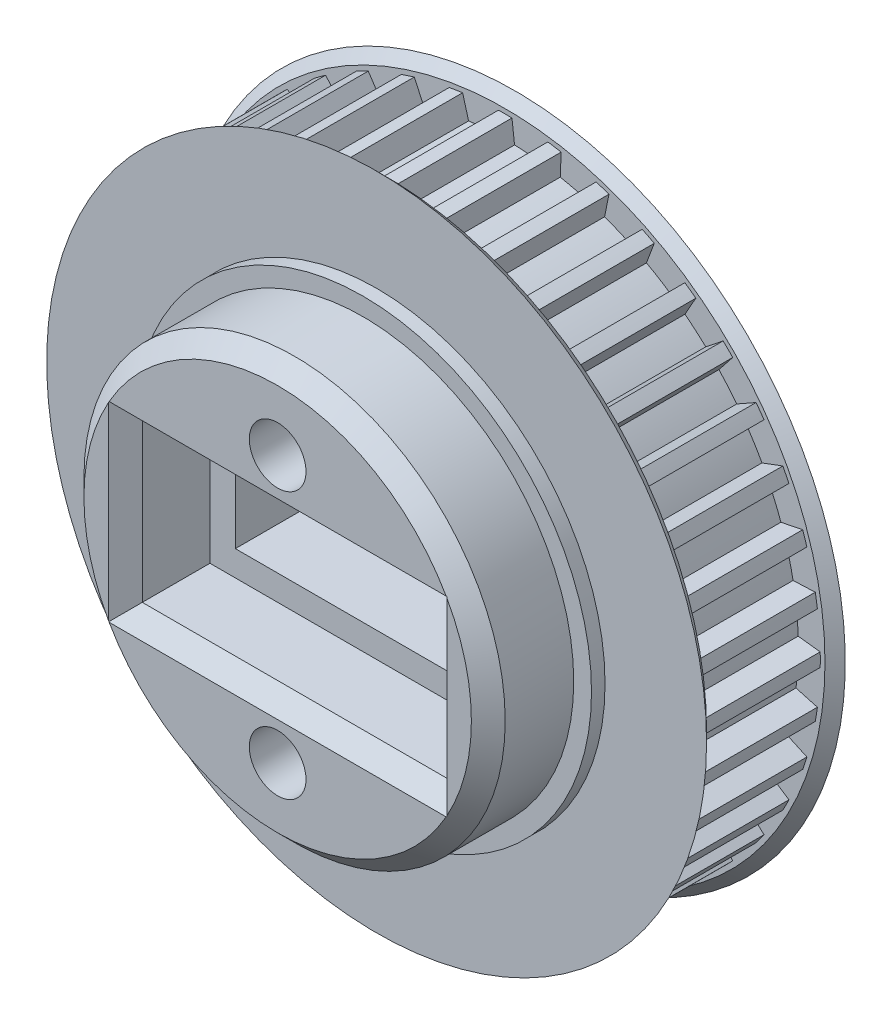
SolidWorks part; units mm, degrees
material "ABS"
ref_plane "Alzado" through (0, 0, 0) normal (0, 0, 1) x (1, 0, 0)
ref_plane "Planta" through (0, 0, 0) normal (0, 1, 0) x (1, 0, 0)
ref_plane "Vista lateral" through (0, 0, 0) normal (1, 0, 0) x (0, 0, -1)
sketch "Croquis1" plane through (0, 0, 0) normal (0, 0, 1) x (1, 0, 0)
  line L0 (0, 0) -> (0, 14.5885) construction
  line L1 (-0.4, 18.6167) -> (-0.55, 17.3123)
  line L2 (0.4, 18.6167) -> (0.55, 17.3123)
  line L3 (3.3074, 18.3249) -> (3.2515, 17.0131)
  line L4 (2.5172, 18.4501) -> (2.165, 17.1852)
  line L5 (6.1333, 17.5819) -> (5.8729, 16.295)
  line L6 (5.3725, 17.8291) -> (4.8267, 16.6349)
  line L7 (8.8082, 16.406) -> (8.3497, 15.1756)
  line L8 (8.0954, 16.7692) -> (7.3695, 15.675)
  line L9 (11.2662, 14.8261) -> (10.6209, 13.6826)
  line L10 (10.619, 15.2963) -> (9.7309, 14.3292)
  line L11 (13.4468, 12.8812) -> (12.6305, 11.8527)
  line L12 (12.8812, 13.4468) -> (11.8527, 12.6305)
  line L13 (15.2963, 10.619) -> (14.3292, 9.7309)
  line L14 (14.8261, 11.2662) -> (13.6826, 10.6209)
  line L15 (16.7692, 8.0954) -> (15.675, 7.3695)
  line L16 (16.406, 8.8082) -> (15.1756, 8.3497)
  line L17 (17.8291, 5.3725) -> (16.6349, 4.8267)
  line L18 (17.5819, 6.1333) -> (16.295, 5.8729)
  line L19 (18.4501, 2.5172) -> (17.1852, 2.165)
  line L20 (18.3249, 3.3074) -> (17.0131, 3.2515)
  line L21 (18.6167, -0.4) -> (17.3123, -0.55)
  line L22 (18.6167, 0.4) -> (17.3123, 0.55)
  line L23 (18.3249, -3.3074) -> (17.0131, -3.2515)
  line L24 (18.4501, -2.5172) -> (17.1852, -2.165)
  line L25 (17.5819, -6.1333) -> (16.295, -5.8729)
  line L26 (17.8291, -5.3725) -> (16.6349, -4.8267)
  line L27 (16.406, -8.8082) -> (15.1756, -8.3497)
  line L28 (16.7692, -8.0954) -> (15.675, -7.3695)
  line L29 (14.8261, -11.2662) -> (13.6826, -10.6209)
  line L30 (15.2963, -10.619) -> (14.3292, -9.7309)
  line L31 (12.8812, -13.4468) -> (11.8527, -12.6305)
  line L32 (13.4468, -12.8812) -> (12.6305, -11.8527)
  line L33 (10.619, -15.2963) -> (9.7309, -14.3292)
  line L34 (11.2662, -14.8261) -> (10.6209, -13.6826)
  line L35 (8.0954, -16.7692) -> (7.3695, -15.675)
  line L36 (8.8082, -16.406) -> (8.3497, -15.1756)
  line L37 (5.3725, -17.8291) -> (4.8267, -16.6349)
  line L38 (6.1333, -17.5819) -> (5.8729, -16.295)
  line L39 (2.5172, -18.4501) -> (2.165, -17.1852)
  line L40 (3.3074, -18.3249) -> (3.2515, -17.0131)
  line L41 (-0.4, -18.6167) -> (-0.55, -17.3123)
  line L42 (0.4, -18.6167) -> (0.55, -17.3123)
  line L43 (-3.3074, -18.3249) -> (-3.2515, -17.0131)
  line L44 (-2.5172, -18.4501) -> (-2.165, -17.1852)
  line L45 (-6.1333, -17.5819) -> (-5.8729, -16.295)
  line L46 (-5.3725, -17.8291) -> (-4.8267, -16.6349)
  line L47 (-8.8082, -16.406) -> (-8.3497, -15.1756)
  line L48 (-8.0954, -16.7692) -> (-7.3695, -15.675)
  line L49 (-11.2662, -14.8261) -> (-10.6209, -13.6826)
  line L50 (-10.619, -15.2963) -> (-9.7309, -14.3292)
  line L51 (-13.4468, -12.8812) -> (-12.6305, -11.8527)
  line L52 (-12.8812, -13.4468) -> (-11.8527, -12.6305)
  line L53 (-15.2963, -10.619) -> (-14.3292, -9.7309)
  line L54 (-14.8261, -11.2662) -> (-13.6826, -10.6209)
  line L55 (-16.7692, -8.0954) -> (-15.675, -7.3695)
  line L56 (-16.406, -8.8082) -> (-15.1756, -8.3497)
  line L57 (-17.8291, -5.3725) -> (-16.6349, -4.8267)
  line L58 (-17.5819, -6.1333) -> (-16.295, -5.8729)
  line L59 (-18.4501, -2.5172) -> (-17.1852, -2.165)
  line L60 (-18.3249, -3.3074) -> (-17.0131, -3.2515)
  line L61 (-18.6167, 0.4) -> (-17.3123, 0.55)
  line L62 (-18.6167, -0.4) -> (-17.3123, -0.55)
  line L63 (-18.3249, 3.3074) -> (-17.0131, 3.2515)
  line L64 (-18.4501, 2.5172) -> (-17.1852, 2.165)
  line L65 (-17.5819, 6.1333) -> (-16.295, 5.8729)
  line L66 (-17.8291, 5.3725) -> (-16.6349, 4.8267)
  line L67 (-16.406, 8.8082) -> (-15.1756, 8.3497)
  line L68 (-16.7692, 8.0954) -> (-15.675, 7.3695)
  line L69 (-14.8261, 11.2662) -> (-13.6826, 10.6209)
  line L70 (-15.2963, 10.619) -> (-14.3292, 9.7309)
  line L71 (-12.8812, 13.4468) -> (-11.8527, 12.6305)
  line L72 (-13.4468, 12.8812) -> (-12.6305, 11.8527)
  line L73 (-10.619, 15.2963) -> (-9.7309, 14.3292)
  line L74 (-11.2662, 14.8261) -> (-10.6209, 13.6826)
  line L75 (-8.0954, 16.7692) -> (-7.3695, 15.675)
  line L76 (-8.8082, 16.406) -> (-8.3497, 15.1756)
  line L77 (-5.3725, 17.8291) -> (-4.8267, 16.6349)
  line L78 (-6.1333, 17.5819) -> (-5.8729, 16.295)
  line L79 (-11.2662, 14.8261) -> (-10.619, 15.2963)
  line L80 (-8.8082, 16.406) -> (-8.0954, 16.7692)
  line L81 (-6.1333, 17.5819) -> (-5.3725, 17.8291)
  line L82 (-2.5172, 18.4501) -> (-2.165, 17.1852)
  line L83 (-3.3074, 18.3249) -> (-3.2515, 17.0131)
  line L84 (-3.3074, 18.3249) -> (-2.5172, 18.4501)
  arc A0 (-17.5819, 6.1333) -> (-17.8291, 5.3725) centre (0, 0) ccw
  arc A1 (2.165, 17.1852) -> (0.55, 17.3123) centre (0, 0) ccw
  arc A2 (-18.3249, 3.3074) -> (-18.4501, 2.5172) centre (0, 0) ccw
  arc A3 (-18.6167, 0.4) -> (-18.6167, -0.4) centre (0, 0) ccw
  arc A4 (-18.4501, -2.5172) -> (-18.3249, -3.3074) centre (0, 0) ccw
  arc A5 (-17.8291, -5.3725) -> (-17.5819, -6.1333) centre (0, 0) ccw
  arc A6 (-16.7692, -8.0954) -> (-16.406, -8.8082) centre (0, 0) ccw
  arc A7 (-15.2963, -10.619) -> (-14.8261, -11.2662) centre (0, 0) ccw
  arc A8 (-13.4468, -12.8812) -> (-12.8812, -13.4468) centre (0, 0) ccw
  arc A9 (-11.2662, -14.8261) -> (-10.619, -15.2963) centre (0, 0) ccw
  arc A10 (-8.8082, -16.406) -> (-8.0954, -16.7692) centre (0, 0) ccw
  arc A11 (3.3074, 18.3249) -> (2.5172, 18.4501) centre (0, 0) ccw
  arc A12 (0.4, 18.6167) -> (-0.4, 18.6167) centre (0, 0) ccw
  arc A13 (-14.8261, 11.2662) -> (-15.2963, 10.619) centre (0, 0) ccw
  arc A14 (-16.406, 8.8082) -> (-16.7692, 8.0954) centre (0, 0) ccw
  arc A15 (-12.8812, 13.4468) -> (-13.4468, 12.8812) centre (0, 0) ccw
  arc A16 (6.1333, 17.5819) -> (5.3725, 17.8291) centre (0, 0) ccw
  arc A17 (8.8082, 16.406) -> (8.0954, 16.7692) centre (0, 0) ccw
  arc A18 (11.2662, 14.8261) -> (10.619, 15.2963) centre (0, 0) ccw
  arc A19 (13.4468, 12.8812) -> (12.8812, 13.4468) centre (0, 0) ccw
  arc A20 (15.2963, 10.619) -> (14.8261, 11.2662) centre (0, 0) ccw
  arc A21 (16.7692, 8.0954) -> (16.406, 8.8082) centre (0, 0) ccw
  arc A22 (17.8291, 5.3725) -> (17.5819, 6.1333) centre (0, 0) ccw
  arc A23 (18.4501, 2.5172) -> (18.3249, 3.3074) centre (0, 0) ccw
  arc A24 (18.6167, -0.4) -> (18.6167, 0.4) centre (0, 0) ccw
  arc A25 (18.3249, -3.3074) -> (18.4501, -2.5172) centre (0, 0) ccw
  arc A26 (12.8812, -13.4468) -> (13.4468, -12.8812) centre (0, 0) ccw
  arc A27 (10.619, -15.2963) -> (11.2662, -14.8261) centre (0, 0) ccw
  arc A28 (8.0954, -16.7692) -> (8.8082, -16.406) centre (0, 0) ccw
  arc A29 (2.5172, -18.4501) -> (3.3074, -18.3249) centre (0, 0) ccw
  arc A30 (-0.4, -18.6167) -> (0.4, -18.6167) centre (0, 0) ccw
  arc A31 (-3.3074, -18.3249) -> (-2.5172, -18.4501) centre (0, 0) ccw
  arc A32 (-6.1333, -17.5819) -> (-5.3725, -17.8291) centre (0, 0) ccw
  arc A33 (14.8261, -11.2662) -> (15.2963, -10.619) centre (0, 0) ccw
  arc A34 (16.406, -8.8082) -> (16.7692, -8.0954) centre (0, 0) ccw
  arc A35 (17.5819, -6.1333) -> (17.8291, -5.3725) centre (0, 0) ccw
  arc A36 (4.8267, 16.6349) -> (3.2515, 17.0131) centre (0, 0) ccw
  arc A37 (7.3695, 15.675) -> (5.8729, 16.295) centre (0, 0) ccw
  arc A38 (-12.6305, 11.8527) -> (-13.6826, 10.6209) centre (0, 0) ccw
  arc A39 (-0.55, 17.3123) -> (-2.165, 17.1852) centre (0, 0) ccw
  arc A40 (-14.3292, 9.7309) -> (-15.1756, 8.3497) centre (0, 0) ccw
  arc A41 (-15.675, 7.3695) -> (-16.295, 5.8729) centre (0, 0) ccw
  arc A42 (-16.6349, 4.8267) -> (-17.0131, 3.2515) centre (0, 0) ccw
  arc A43 (9.7309, 14.3292) -> (8.3497, 15.1756) centre (0, 0) ccw
  arc A44 (11.8527, 12.6305) -> (10.6209, 13.6826) centre (0, 0) ccw
  arc A45 (13.6826, 10.6209) -> (12.6305, 11.8527) centre (0, 0) ccw
  arc A46 (15.1756, 8.3497) -> (14.3292, 9.7309) centre (0, 0) ccw
  arc A47 (16.295, 5.8729) -> (15.675, 7.3695) centre (0, 0) ccw
  arc A48 (17.0131, 3.2515) -> (16.6349, 4.8267) centre (0, 0) ccw
  arc A49 (17.3123, 0.55) -> (17.1852, 2.165) centre (0, 0) ccw
  arc A50 (17.1852, -2.165) -> (17.3123, -0.55) centre (0, 0) ccw
  arc A51 (16.6349, -4.8267) -> (17.0131, -3.2515) centre (0, 0) ccw
  arc A52 (15.675, -7.3695) -> (16.295, -5.8729) centre (0, 0) ccw
  arc A53 (14.3292, -9.7309) -> (15.1756, -8.3497) centre (0, 0) ccw
  arc A54 (12.6305, -11.8527) -> (13.6826, -10.6209) centre (0, 0) ccw
  arc A55 (10.6209, -13.6826) -> (11.8527, -12.6305) centre (0, 0) ccw
  arc A56 (8.3497, -15.1756) -> (9.7309, -14.3292) centre (0, 0) ccw
  arc A57 (5.8729, -16.295) -> (7.3695, -15.675) centre (0, 0) ccw
  arc A58 (3.2515, -17.0131) -> (4.8267, -16.6349) centre (0, 0) ccw
  arc A59 (0.55, -17.3123) -> (2.165, -17.1852) centre (0, 0) ccw
  arc A60 (-2.165, -17.1852) -> (-0.55, -17.3123) centre (0, 0) ccw
  arc A61 (-4.8267, -16.6349) -> (-3.2515, -17.0131) centre (0, 0) ccw
  arc A62 (-7.3695, -15.675) -> (-5.8729, -16.295) centre (0, 0) ccw
  arc A63 (-9.7309, -14.3292) -> (-8.3497, -15.1756) centre (0, 0) ccw
  arc A64 (-11.8527, -12.6305) -> (-10.6209, -13.6826) centre (0, 0) ccw
  arc A65 (-13.6826, -10.6209) -> (-12.6305, -11.8527) centre (0, 0) ccw
  arc A66 (-15.1756, -8.3497) -> (-14.3292, -9.7309) centre (0, 0) ccw
  arc A67 (-16.295, -5.8729) -> (-15.675, -7.3695) centre (0, 0) ccw
  arc A68 (-17.0131, -3.2515) -> (-16.6349, -4.8267) centre (0, 0) ccw
  arc A69 (-17.3123, -0.55) -> (-17.1852, -2.165) centre (0, 0) ccw
  arc A70 (-17.1852, 2.165) -> (-17.3123, 0.55) centre (0, 0) ccw
  arc A71 (5.3725, -17.8291) -> (6.1333, -17.5819) centre (0, 0) ccw
  circle A72 centre (0, 0) radius 2
  arc A73 (-5.8729, 16.295) -> (-7.3695, 15.675) centre (0, 0) ccw
  arc A74 (-8.3497, 15.1756) -> (-9.7309, 14.3292) centre (0, 0) ccw
  arc A75 (-10.6209, 13.6826) -> (-11.8527, 12.6305) centre (0, 0) ccw
  arc A76 (-3.2515, 17.0131) -> (-4.8267, 16.6349) centre (0, 0) ccw
  point P151 (0, 0)
  dimension "D1" = 1.3
  dimension "D6" = 4
  dimension "D2" = 1.1
  dimension "D3" = 0.8
  dimension "D5" = 1.62
  dimension "D4" = 40
extrude "Saliente-Extruir1" add sketch "Croquis1" along normal blind 7
sketch "Croquis2" plane through (0, 0, 7) normal (0, 0, 1) x (1, 0, 0)
  circle A0 centre (0, 0) radius 19.5
  circle A1 centre (0, 0) radius 2
  circle A2 centre (0, 0) radius 2 construction
  dimension "D1" = 39
extrude "Saliente-Extruir2" add sketch "Croquis2" along normal blind 0.6
sketch "Croquis3" plane through (0, 0, 7.6) normal (0, 0, 1) x (1, 0, 0)
  circle A0 centre (0, 0) radius 2
  circle A1 centre (0, 0) radius 12.45
  circle A3 centre (0, 0) radius 2 construction
  dimension "D1" = 24.9
sketch "Croquis4" plane through (0, 0, 0) normal (0, 0, -1) x (-1, 0, 0)
  circle A0 centre (0, 0) radius 2
  circle A1 centre (0, 0) radius 12.45
  circle A2 centre (0, 0) radius 2 construction
  dimension "D1" = 24.9
extrude "Saliente-Extruir4" add sketch "Croquis4" along normal blind 6.2
sketch "Croquis6" plane through (0, 0, 0) normal (0, 0, -1) x (-1, 0, 0)
  circle A0 centre (0, 0) radius 19.5
  circle A1 centre (0, 0) radius 2
  circle A2 centre (0, 0) radius 2 construction
  dimension "D1" = 39
extrude "Saliente-Extruir6" add sketch "Croquis6" along normal blind 0.6
sketch "Croquis5" plane through (0, 0, -0.6) normal (0, 0, -1) x (-1, 0, 0)
  circle A0 centre (0, 0) radius 2
  circle A1 centre (0, 0) radius 13.5
  circle A2 centre (0, 0) radius 2 construction
  dimension "D1" = 27
extrude "Saliente-Extruir5" add sketch "Croquis5" along normal blind 0.6
extrude "Saliente-Extruir7" add sketch "Croquis3" along normal blind 5.85
chamfer "Chaflán4" distance 1 angle 45 2 edges at (-12.45, 0, -6.2) (12.45, 0, 13.45)
sketch "Croquis7" plane through (0, 0, 7.6) normal (0, 0, 1) x (1, 0, 0)
  circle A0 centre (0, 0) radius 2
  circle A1 centre (0, 0) radius 13.5
  circle A2 centre (0, 0) radius 2 construction
  dimension "D1" = 27
extrude "Saliente-Extruir8" add sketch "Croquis7" along normal blind 0.8
sketch "Croquis8" plane through (0, 0, 0) normal (0, 0, 1) x (1, 0, 0)
  line L0 (0, 0) -> (6.706, 0) construction
  line L1 (-7.5, 3.15) -> (7.5, 3.15)
  line L2 (-7.5, 3.15) -> (-7.5, -3.15)
  line L3 (-7.5, -3.15) -> (7.5, -3.15)
  line L4 (7.5, 3.15) -> (7.5, -3.15)
  line L5 (-7.5, 3.15) -> (7.5, -3.15) construction
  line L6 (-7.5, -3.15) -> (7.5, 3.15) construction
  circle A0 centre (0, 7.8756) radius 1.675
  circle A1 centre (0, -7.8756) radius 1.675
  point P0 (0, 0)
  dimension "D1" = 3.35
  dimension "D2" = 6.3
  dimension "D3" = 15
extrude "Cortar-Extruir1" cut sketch "Croquis8" against normal through all both and the other way through all
sketch "Croquis9" plane through (0, 0, -6.2) normal (0, 0, -1) x (-1, 0, 0)
  line L1 (2.3383, 3.8256) -> (4.6765, 7.8756)
  line L2 (4.6765, 7.8756) -> (2.3383, 11.9256)
  line L3 (2.3383, 11.9256) -> (-2.3383, 11.9256)
  line L4 (-2.3383, 11.9256) -> (-4.6765, 7.8756)
  line L5 (-4.6765, 7.8756) -> (-2.3383, 3.8256)
  line L6 (-2.3383, 3.8256) -> (2.3383, 3.8256)
  line L7 (2.3383, -11.9256) -> (4.6765, -7.8756)
  line L8 (4.6765, -7.8756) -> (2.3383, -3.8256)
  line L9 (2.3383, -3.8256) -> (-2.3383, -3.8256)
  line L10 (-2.3383, -3.8256) -> (-4.6765, -7.8756)
  line L11 (-4.6765, -7.8756) -> (-2.3383, -11.9256)
  line L12 (-2.3383, -11.9256) -> (2.3383, -11.9256)
  circle A0 centre (0, 7.8756) radius 4.05 construction
  circle A1 centre (0, -7.8756) radius 4.05 construction
  dimension "D1" = 8.1
extrude "Cortar-Extruir2" cut sketch "Croquis9" against normal blind 5
fillet "Redondeo1" radius 2.5 12 edges at (3.5074, -9.9006, -1.2) (3.5074, -5.8506, -1.2) (0, -3.8256, -1.2) (-3.5074, -5.8506, -1.2) (0, -11.9256, -1.2) (-3.5074, -9.9006, -1.2) (-3.5074, 5.8506, -1.2) (-3.5074, 9.9006, -1.2) (0, 11.9256, -1.2) (3.5074, 9.9006, -1.2) (3.5074, 5.8506, -1.2) (0, 3.8256, -1.2)
sketch "Croquis10" plane through (0, 0, 13.45) normal (0, 0, 1) x (1, 0, 0)
  line L0 (7.5, 3.15) -> (-7.5, 3.15) construction
  line L1 (9, 4.65) -> (-9, 4.65)
  line L2 (9, 4.65) -> (9, -4.65)
  line L3 (9, -4.65) -> (-9, -4.65)
  line L4 (-9, 4.65) -> (-9, -4.65)
  line L5 (9, 4.65) -> (-9, -4.65) construction
  line L6 (9, -4.65) -> (-9, 4.65) construction
  line L7 (-7.5, 3.15) -> (-7.5, -3.15) construction
  point P0 (0, 0)
  dimension "D1" = 1.5
  dimension "D2" = 1.5
extrude "Cortar-Extruir3" cut sketch "Croquis10" against normal blind 5
chamfer "Chaflán5" distance 1 angle 45 8 edges at (-7.5, 0, -6.2) (0, 3.15, -6.2) (7.5, 0, -6.2) (0, -3.15, -6.2) (9, 0, 13.45) (0, 4.65, 13.45) (-9, 0, 13.45) (0, -4.65, 13.45)
chamfer "Chaflán6" distance 0.6 angle 45 2 edges at (19.5, 0, 7) (-19.5, 0, 0)
